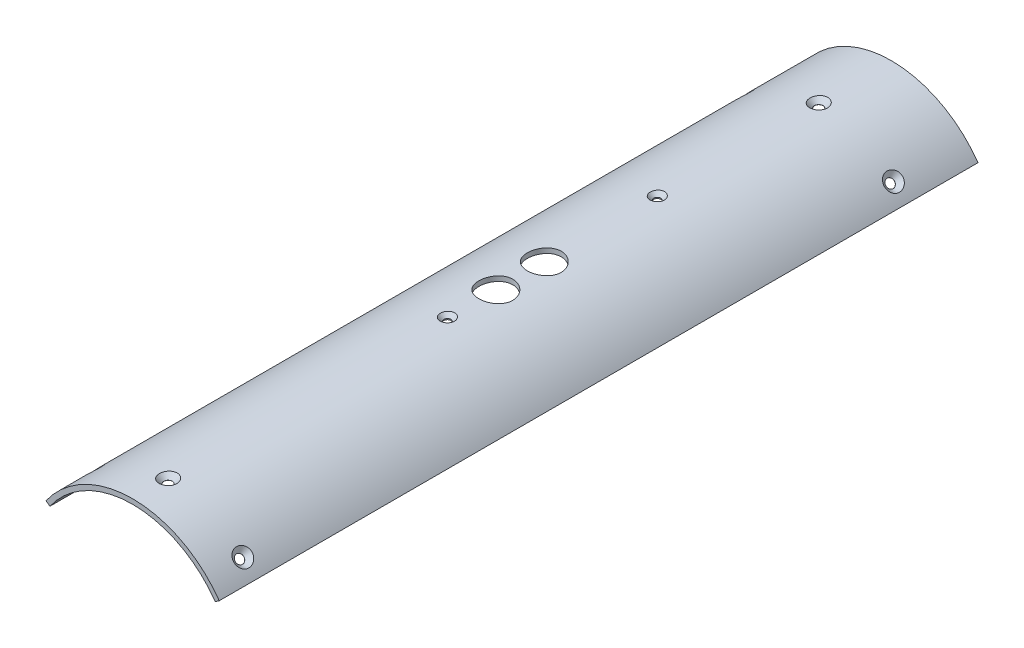
SolidWorks part; units mm, degrees
material "Cam Elyaf Real"
ref_plane "Ön Düzlem" through (0, 0, 0) normal (0, 0, 1) x (1, 0, 0)
ref_plane "Üst Düzlem" through (0, 0, 0) normal (0, 1, 0) x (1, 0, 0)
ref_plane "Sağ Düzlem" through (0, 0, 0) normal (1, 0, 0) x (0, 0, -1)
sketch "Çizim1" plane through (0, 0, 0) normal (0, 0, 1) x (1, 0, 0)
  circle A0 centre (0, 0) radius 62.5
  dimension "D1" = 125
extrude "Ekstrüzyon-İnce1" add sketch "Çizim1" along normal blind 470 thin thin type one direction wall 3
ref_plane "Düzlem1" through (0, 65.5, 0) normal (0, 1, 0) x (1, 0, 0)
sketch "Çizim2" plane through (0, 65.5, 0) normal (0, 1, 0) x (1, 0, 0)
  line L0 (0, -470) -> (0, -448) construction
  line L1 (-65.5, -470) -> (65.5, -470) construction
  line L2 (0, 0) -> (0, -45) construction
  point P1 (0, -448)
  point P8 (0, -448)
  point P12 (0, -45)
  point P16 (0, -45)
  dimension "D1" = 22
  dimension "D2" = 45
hole_wizard "M5 Altıgen Alyan Havşa Başlı Kör Vida İçin Havşa1" positions "Çizim2" profile "Çizim3" countersink size "M5" standard "ISO"
sketch "Çizim3" plane through (0, 65.5, 45) normal (1, 0, 0) x (0, 0, 1)
  line L0 (0, 0) -> (0, 13.0923)
  line L1 (0, 13.0923) -> (2.65, 11.5)
  line L2 (2.65, 11.5) -> (2.65, 2.95)
  line L3 (2.65, 2.95) -> (5.6, 0)
  line L5 (5.6, 0) -> (0, 0)
  line L6 (-2.65, 2.95) -> (-5.6, 0) construction
  line L10 (0, 13.0923) -> (-2.65, 11.5) construction
  line L11 (0, -6.35) -> (0, 107.95) construction
  dimension "Hole Dia." = 5.3
  dimension "Hole Depth" = 11.5
  dimension "Near C'Sink Dia." = 11.2
  dimension "Near C'Sink Angle" = 90
  dimension "Drill Angle" = 118
pattern_circular "Dairesel Kaplama1" count 8 over 360 about axis through (0, 0, 470) along (0, 0, 1) of "M5 Altıgen Alyan Havşa Başlı Kör Vida İçin Havşa1"
sketch "Çizim4" plane through (0, 65.5, 0) normal (0, 1, 0) x (1, 0, 0)
  line L0 (0, -470) -> (0, -275) construction
  line L1 (-65.5, -470) -> (65.5, -470) construction
  point P1 (0, -275)
  point P8 (0, -275)
  dimension "D1" = 195
hole_wizard "M4 Altıgen Alyan Havşa Başlı Kör Vida İçin Havşa3" positions "Çizim4" profile "Çizim5" countersink size "M4" standard "ISO"
sketch "Çizim5" plane through (0, 65.5, 275) normal (1, 0, 0) x (0, 0, 1)
  line L0 (0, 0) -> (0, 12.7919)
  line L1 (0, 12.7919) -> (2.15, 11.5)
  line L2 (2.15, 11.5) -> (2.15, 2.33)
  line L3 (2.15, 2.33) -> (4.48, 0)
  line L5 (4.48, 0) -> (0, 0)
  line L6 (-2.15, 2.33) -> (-4.48, 0) construction
  line L10 (0, 12.7919) -> (-2.15, 11.5) construction
  line L11 (0, -6.35) -> (0, 107.95) construction
  dimension "Hole Dia." = 4.3
  dimension "Hole Depth" = 11.5
  dimension "Near C'Sink Dia." = 8.96
  dimension "Near C'Sink Angle" = 90
  dimension "Drill Angle" = 118
sketch "Çizim6" plane through (0, 65.5, 0) normal (0, 1, 0) x (1, 0, 0)
  line L0 (0, -470) -> (0, -145) construction
  line L1 (-65.5, -470) -> (65.5, -470) construction
  point P1 (0, -145)
  point P9 (0, -145)
  dimension "D1" = 325
hole_wizard "M4 Altıgen Alyan Havşa Başlı Kör Vida İçin Havşa5" positions "Çizim6" profile "Çizim7" countersink size "M4" standard "ISO"
sketch "Çizim7" plane through (0, 65.5, 145) normal (1, 0, 0) x (0, 0, 1)
  line L0 (0, 0) -> (0, 12.7919)
  line L1 (0, 12.7919) -> (2.15, 11.5)
  line L2 (2.15, 11.5) -> (2.15, 2.33)
  line L3 (2.15, 2.33) -> (4.48, 0)
  line L5 (4.48, 0) -> (0, 0)
  line L6 (-2.15, 2.33) -> (-4.48, 0) construction
  line L10 (0, 12.7919) -> (-2.15, 11.5) construction
  line L11 (0, -6.35) -> (0, 107.95) construction
  dimension "Hole Dia." = 4.3
  dimension "Hole Depth" = 11.5
  dimension "Near C'Sink Dia." = 8.96
  dimension "Near C'Sink Angle" = 90
  dimension "Drill Angle" = 118
pattern_circular "Dairesel Kaplama2" count 4 over 360 about axis through (0, 0, 470) along (0, 0, 1) of "M4 Altıgen Alyan Havşa Başlı Kör Vida İçin Havşa5"
sketch "Çizim8" plane through (0, 65.5, 0) normal (0, 1, 0) x (1, 0, 0)
  line L0 (0, -275) -> (0, -245) construction
  line L2 (0, -245) -> (0, -215) construction
  circle A0 centre (0, -245) radius 10.5
  circle A1 centre (0, -215) radius 10.5
  dimension "D3" = 21
  dimension "D4" = 21
  dimension "D1" = 30
  dimension "D2" = 30
extrude "Kes-Ekstrüzyon1" cut sketch "Çizim8" against normal blind 10
sketch "Çizim12" plane through (0, 0, 0) normal (0, 0, -1) x (-1, 0, 0)
  line L0 (0, 0) -> (0, 55) construction
  line L1 (0, 0) -> (53.6545, 37.5693) construction
  line L2 (0, 0) -> (-53.6545, 37.5693) construction
  line L3 (-53.6545, 37.5693) -> (-51.197, 35.8485)
  line L4 (53.6545, 37.5693) -> (51.197, 35.8485)
  circle A0 centre (0, 0) radius 65.5 construction
  arc A1 (-53.6545, 37.5693) -> (53.6545, 37.5693) centre (0, 0) ccw
  arc A2 (-51.197, 35.8485) -> (51.197, 35.8485) centre (0, 0) ccw
  dimension "D1" = 55
  dimension "D2" = 55
extrude "Kes-Ekstrüzyon3" cut sketch "Çizim12" against normal through all
